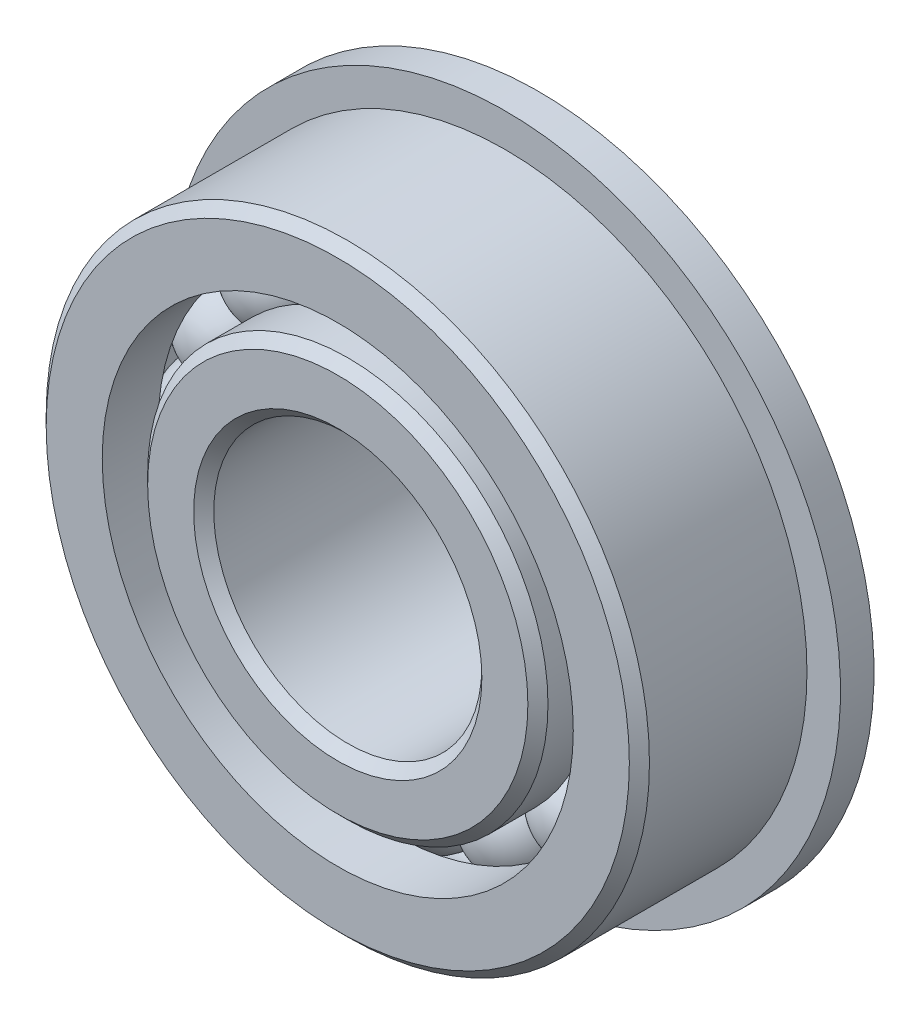
SolidWorks part; units mm, degrees
ref_plane "Front Plane" through (0, 0, 0) normal (0, 0, 1) x (1, 0, 0)
ref_plane "Top Plane" through (0, 0, 0) normal (0, 1, 0) x (1, 0, 0)
ref_plane "Right Plane" through (0, 0, 0) normal (1, 0, 0) x (0, 0, -1)
sketch "Sketch1" plane through (0, 0, 0) normal (1, 0, 0) x (0, 0, -1)
  line L0 (-4.7625, 0) -> (4.7625, 0) construction
  line L1 (0, 14.2875) -> (0, -14.2875) construction
  line L2 (4.2863, 14.2875) -> (-4.2863, 14.2875)
  line L3 (-4.2863, 14.2875) -> (-4.7625, 13.8113)
  line L4 (-4.7625, 13.8113) -> (-4.7625, 11.1561)
  line L5 (-4.7625, 11.1561) -> (-2.1167, 11.1561)
  line L6 (4.7625, 11.1561) -> (2.1167, 11.1561)
  line L7 (4.7625, 13.8113) -> (4.7625, 11.1561)
  line L8 (4.2863, 14.2875) -> (4.7625, 13.8113)
  line L9 (0, 14.2875) -> (0, 10.3187) construction
  line L10 (0, 10.3187) -> (0, 6.35) construction
  arc A0 (-2.1167, 11.1561) -> (2.1167, 11.1561) centre (0, 10.3187) cw
  point P14 (0, 6.35)
  dimension "D3" = 4.2333
  dimension "D1" = 45
  dimension "Width" = 9.525
  dimension "OD" = 28.575
  dimension "D2" = 0.4763
  dimension "Shaft Dia" = 12.7
  dimension "D4" = 0.8374
revolve "Revolve1" add sketch "Sketch1" angle 360 about L0
sketch "Sketch3" plane through (0, 0, 0) normal (1, 0, 0) x (0, 0, -1)
  line L0 (-2.1167, 9.4814) -> (-4.7625, 9.4814) construction
  line L1 (-4.7625, 13.8113) -> (-4.7625, 11.1561) construction
  line L2 (-4.2863, 14.2875) -> (-4.7625, 13.8113) construction
  line L3 (-4.7625, 9.4814) -> (-4.7625, 6.8263) construction
  line L4 (-4.7625, 6.8263) -> (-4.7625, 9.0051)
  line L5 (-4.7625, 6.8263) -> (-4.2863, 6.35)
  line L6 (-4.2863, 6.35) -> (5.8737, 6.35)
  line L7 (-4.7625, 13.8113) -> (-4.7625, -13.8113) construction
  line L8 (5.8737, 6.35) -> (6.35, 6.8262)
  line L10 (6.35, 6.8262) -> (6.35, 9.4814) construction
  line L11 (6.35, 9.4814) -> (2.1167, 9.4814) construction
  line L12 (0, 14.2875) -> (0, -14.2875) construction
  line L13 (4.2863, 14.2875) -> (4.7625, 13.8113) construction
  line L14 (-4.7625, 9.0051) -> (-4.2863, 9.4814)
  line L15 (-4.2863, 9.4814) -> (-2.1167, 9.4814)
  line L16 (2.1167, 9.4814) -> (5.8737, 9.4814)
  line L17 (5.8737, 9.4814) -> (6.35, 9.0051)
  line L18 (6.35, 9.0051) -> (6.35, 6.8262)
  arc A1 (2.1167, 9.4814) -> (-2.1167, 9.4814) centre (0, 10.3187) cw
  arc A2 (2.1167, 11.1561) -> (-2.1167, 11.1561) centre (0, 10.3187) ccw construction
  dimension "D1" = 45
  dimension "Ring Wd" = 11.1125
revolve "Revolve3" add sketch "Sketch3" angle 360 about L0
sketch "Sketch4" plane through (0, 0, 0) normal (1, 0, 0) x (0, 0, -1)
  line L0 (-2.2763, 10.3187) -> (2.2763, 10.3187)
  arc A2 (-2.2763, 10.3187) -> (2.2763, 10.3187) centre (0, 10.3187) cw
  arc A3 (2.1167, 11.1561) -> (-2.1167, 11.1561) centre (0, 10.3187) ccw construction
revolve "Revolve4" add sketch "Sketch4" angle 360 about L0
ref_axis "Axis1" through (0, 0, -4.7625) along (0, 0, 1)
pattern_circular "CirPattern1" count 16 every 22.5 about axis through (0, 0, -4.7625) along (0, 0, 1) of bodies 104
sketch "Sketch5" plane through (0, 0, 0) normal (1, 0, 0) x (0, 0, -1)
  line L0 (-4.7625, 11.1561) -> (-2.1167, 11.1561) construction
  line L1 (-4.5244, 11.1561) -> (-2.2763, 11.1561)
  line L2 (-4.5244, 11.1561) -> (-4.5244, 9.4814)
  line L3 (-4.5244, 9.4814) -> (-2.2763, 9.4814)
  line L4 (-2.2763, 11.1561) -> (-2.2763, 9.4814)
  line L5 (-2.1167, 9.4814) -> (-4.7625, 9.4814) construction
  line L6 (4.7625, 11.1561) -> (2.1167, 11.1561) construction
  line L7 (4.5244, 11.1561) -> (2.2763, 11.1561)
  line L8 (4.5244, 11.1561) -> (4.5244, 9.4814)
  line L9 (4.5244, 9.4814) -> (2.2763, 9.4814)
  line L10 (2.2763, 11.1561) -> (2.2763, 9.4814)
  line L11 (6.35, 9.4814) -> (2.1167, 9.4814) construction
  line L12 (-4.2863, 14.2875) -> (-4.7625, 13.8113) construction
  point P18 (-4.5244, 14.0494)
revolve "Revolve5" [suppressed] add sketch "Sketch5" angle 360 about L0
sketch "Sketch6" plane through (0, 0, 0) normal (1, 0, 0) x (0, 0, -1)
  line L1 (4.7625, 11.1561) -> (3.175, 11.1561)
  line L2 (4.7625, 11.1561) -> (4.7625, 15.875)
  line L3 (4.7625, 15.875) -> (3.175, 15.875)
  line L4 (3.175, 11.1561) -> (3.175, 15.875)
  line L5 (4.7625, 0) -> (-4.7625, 0) construction
  dimension "Flange OD" = 31.75
  dimension "Th" = 1.5875
revolve "Revolve6" add sketch "Sketch6" angle 360 about L5
equation "\"D2@Sketch1\" = \"Width@Sketch1\"*.05"
equation "\"D3@Sketch1\" = \"Width@Sketch1\"/2.25"
equation "\"D4@Sketch1\" = (((\"OD@Sketch1\"-\"Width@Sketch1\")/2)/3.25)/3.5"
equation "\"D2@CirPattern1\" = 360/\"Balls@CirPattern1\""
